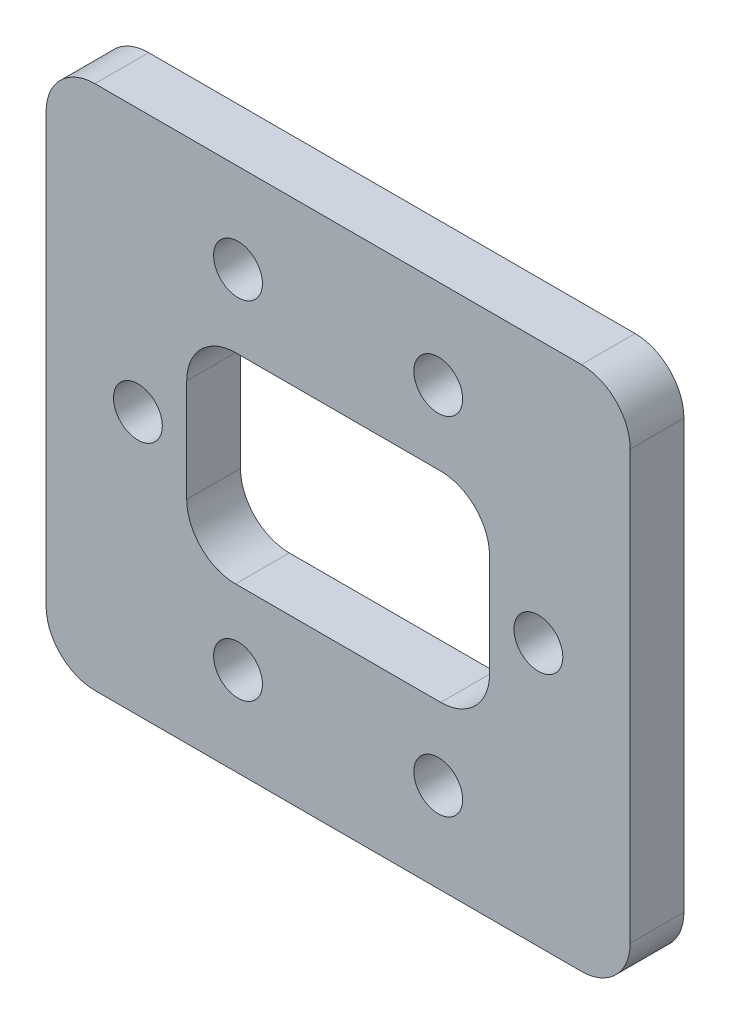
SolidWorks part; units mm, degrees
ref_plane "前基準面" through (0, 0, 0) normal (0, 0, 1) x (1, 0, 0)
ref_plane "上基準面" through (0, 0, 0) normal (0, 1, 0) x (1, 0, 0)
ref_plane "右基準面" through (0, 0, 0) normal (1, 0, 0) x (0, 0, -1)
sketch "草圖1" plane through (0, 0, 0) normal (0, 0, 1) x (1, 0, 0)
  line L0 (-28.8779, 27.6748) -> (30.9221, 27.6748)
  line L1 (-9.4779, 11.0283) -> (11.5221, 11.0283)
  line L2 (-14.4779, 6.0283) -> (-14.4779, -4.4788)
  line L3 (-9.4779, -9.4788) -> (11.5221, -9.4788)
  line L4 (16.5221, 6.0283) -> (16.5221, -4.4788)
  line L5 (-14.4779, 11.0283) -> (16.5221, -9.4788) construction
  line L6 (-14.4779, -9.4788) -> (16.5221, 11.0283) construction
  line L7 (-14.4779, 26.0283) -> (16.5221, 26.0283)
  line L8 (-24.4779, 16.0283) -> (-24.4779, -14.4788)
  line L9 (-14.4779, -24.4788) -> (16.5221, -24.4788)
  line L10 (26.5221, 16.0283) -> (26.5221, -14.4788)
  line L11 (-24.4779, 26.0283) -> (26.5221, -24.4788) construction
  line L12 (-24.4779, -24.4788) -> (26.5221, 26.0283) construction
  line L14 (-36.9779, 30.7748) -> (39.0221, -29.2252) construction
  line L15 (-36.9779, -29.2252) -> (39.0221, 30.7748) construction
  line L16 (-33.8779, 22.6748) -> (-33.8779, -21.1252)
  line L17 (-28.8779, -26.1252) -> (30.9221, -26.1252)
  line L18 (35.9221, 22.6748) -> (35.9221, -21.1252)
  circle A0 centre (1.0221, 0.7748) radius 0.353 construction
  circle A1 centre (21.5221, 0.7748) radius 2.5
  circle A2 centre (-19.4779, 0.7748) radius 2.5
  arc A3 (-24.4779, -14.4788) -> (-14.4779, -24.4788) centre (-14.4779, -14.4788) ccw
  arc A4 (16.5221, -24.4788) -> (26.5221, -14.4788) centre (16.5221, -14.4788) ccw
  arc A5 (16.5221, 26.0283) -> (26.5221, 16.0283) centre (16.5221, 16.0283) cw
  arc A6 (-14.4779, 26.0283) -> (-24.4779, 16.0283) centre (-14.4779, 16.0283) ccw
  arc A7 (-9.4779, 11.0283) -> (-14.4779, 6.0283) centre (-9.4779, 6.0283) ccw
  arc A8 (-14.4779, -4.4788) -> (-9.4779, -9.4788) centre (-9.4779, -4.4788) ccw
  arc A9 (11.5221, -9.4788) -> (16.5221, -4.4788) centre (11.5221, -4.4788) ccw
  arc A10 (11.5221, 11.0283) -> (16.5221, 6.0283) centre (11.5221, 6.0283) cw
  arc A11 (-33.8779, -21.1252) -> (-28.8779, -26.1252) centre (-28.8779, -21.1252) ccw
  arc A12 (30.9221, -26.1252) -> (35.9221, -21.1252) centre (30.9221, -21.1252) ccw
  arc A13 (35.9221, 22.6748) -> (30.9221, 27.6748) centre (30.9221, 22.6748) ccw
  arc A14 (-28.8779, 27.6748) -> (-33.8779, 22.6748) centre (-28.8779, 22.6748) ccw
  circle A15 centre (11.2721, 18.5283) radius 2.5
  circle A16 centre (11.2721, -16.9788) radius 2.5
  circle A17 centre (-9.2279, -16.9788) radius 2.5
  circle A18 centre (-9.2279, 18.5283) radius 2.5
  point P8 (1.0221, 0.7748)
  point P13 (1.0221, 0.7748)
  point P15 (1.0221, 0.7748)
  point P65 (1.0221, 0.7748)
  dimension "D1" = 0.706
  dimension "D2" = 5
  dimension "D4" = 5
  dimension "D7" = 10
  dimension "D8" = 5
  dimension "D9" = 5
  dimension "D12" = 5
  dimension "D11" = 5
  dimension "D17" = 5
  dimension "D18" = 5
  dimension "D19" = 5
  dimension "D3" = 20.5
  dimension "D5" = 20.5
  dimension "D6" = 5
  dimension "D10" = 5
  dimension "D13" = 7.5
  dimension "D14" = 7.5
  dimension "D15" = 17.7535
  dimension "D16" = 20.5
extrude "填料-伸長1" add sketch "草圖1" along normal blind 5.5 contours L0 A14 L16 A11 L17 A12 L18 A13 A6 L7 A5 L10 A4 L9 A3 L8 | L7 A6 L8 A3 L9 A4 L10 A5 A18 A17 A16 A15 A1 A2 L1 A10 L4 A9 L3 A8 L2 A7 region at (1.0221, 26.7935, 0) region at (1.0221, 25.3105, 0)
sketch "草圖24" plane through (0, 0, 5.5) normal (0, 0, 1) x (1, 0, 0)
  line L0 (-28.8779, 22.6748) -> (-28.8779, -21.1252)
  line L1 (-23.8779, 27.6748) -> (25.9221, 27.6748)
  line L2 (-23.8779, -26.1252) -> (25.9221, -26.1252)
  line L3 (30.9221, 22.6748) -> (30.9221, -21.1252)
  line L4 (30.9221, 27.6748) -> (-28.8779, 27.6748)
  line L5 (-33.8779, 22.6748) -> (-33.8779, -21.1252)
  line L6 (-28.8779, -26.1252) -> (30.9221, -26.1252)
  line L7 (35.9221, -21.1252) -> (35.9221, 22.6748)
  line L8 (30.9221, 27.6748) -> (-28.8779, 27.6748)
  line L9 (-33.8779, 22.6748) -> (-33.8779, -21.1252)
  line L10 (-28.8779, -26.1252) -> (30.9221, -26.1252)
  line L11 (35.9221, -21.1252) -> (35.9221, 22.6748)
  arc A0 (-28.8779, -21.1252) -> (-23.8779, -26.1252) centre (-23.8779, -21.1252) ccw
  arc A1 (-28.8779, 22.6748) -> (-23.8779, 27.6748) centre (-23.8779, 22.6748) cw
  arc A2 (30.9221, 22.6748) -> (25.9221, 27.6748) centre (25.9221, 22.6748) ccw
  arc A3 (30.9221, -21.1252) -> (25.9221, -26.1252) centre (25.9221, -21.1252) cw
  arc A4 (-28.8779, 27.6748) -> (-33.8779, 22.6748) centre (-28.8779, 22.6748) ccw
  arc A5 (-33.8779, -21.1252) -> (-28.8779, -26.1252) centre (-28.8779, -21.1252) ccw
  arc A6 (30.9221, -26.1252) -> (35.9221, -21.1252) centre (30.9221, -21.1252) ccw
  arc A7 (35.9221, 22.6748) -> (30.9221, 27.6748) centre (30.9221, 22.6748) ccw
  arc A8 (-28.8779, 27.6748) -> (-33.8779, 22.6748) centre (-28.8779, 22.6748) ccw
  arc A9 (-33.8779, -21.1252) -> (-28.8779, -26.1252) centre (-28.8779, -21.1252) ccw
  arc A10 (30.9221, -26.1252) -> (35.9221, -21.1252) centre (30.9221, -21.1252) ccw
  arc A11 (35.9221, 22.6748) -> (30.9221, 27.6748) centre (30.9221, 22.6748) ccw
  point P15 (1.0221, 27.6748)
  point P26 (1.0221, -26.1252)
  point P27 (1.0221, -26.1252)
  point P28 (1.0221, 27.6748)
  line M9 (30.9221, 27.6748) -> (-28.8779, 27.6748)
  arc M10 (-28.8779, 27.6748) -> (-33.8779, 22.6748) centre (-28.8779, 22.6748) ccw
  line M11 (-33.8779, 22.6748) -> (-33.8779, -21.1252)
  arc M12 (-33.8779, -21.1252) -> (-28.8779, -26.1252) centre (-28.8779, -21.1252) ccw
  line M13 (-28.8779, -26.1252) -> (30.9221, -26.1252)
  arc M14 (30.9221, -26.1252) -> (35.9221, -21.1252) centre (30.9221, -21.1252) ccw
  line M15 (35.9221, -21.1252) -> (35.9221, 22.6748)
  arc M16 (35.9221, 22.6748) -> (30.9221, 27.6748) centre (30.9221, 22.6748) ccw
  dimension "D1" = 0
extrude "除料-伸長1" cut sketch "草圖24" against normal blind 10 contours L0 A1 A0 M9 M10 M11 M12 M13 | L3 A3 A2 M13 M14 M15 M16 M9 region at (-31.1784, 0.7748, 5.5) region at (33.2227, 0.7748, 5.5)
